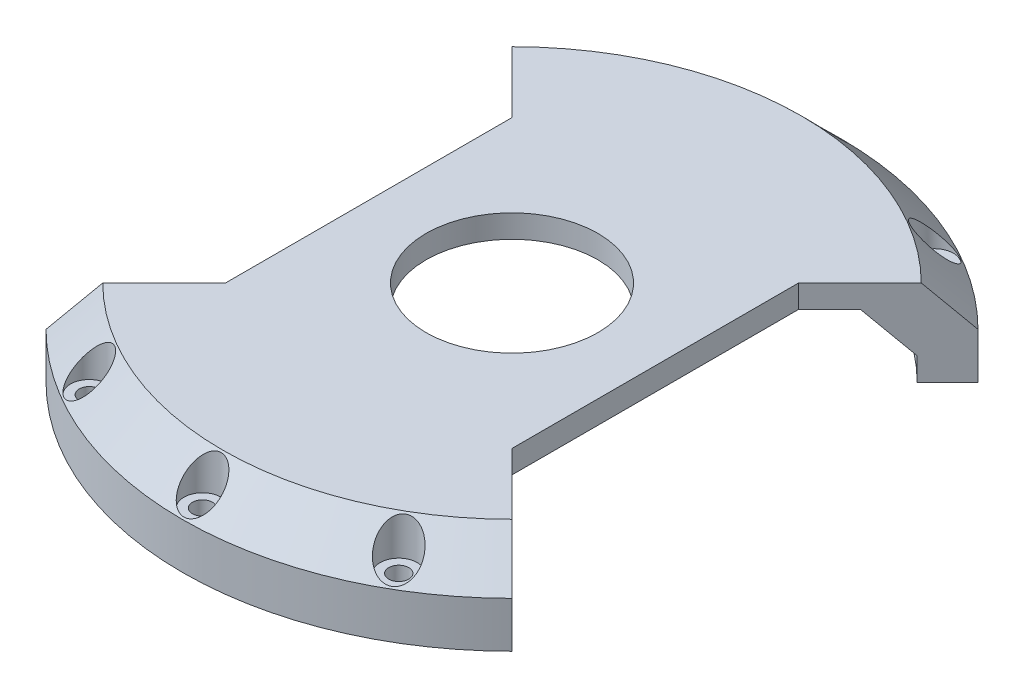
SolidWorks part; units mm, degrees
ref_plane "Front Plane" through (0, 0, 0) normal (0, 0, 1) x (1, 0, 0)
ref_plane "Top Plane" through (0, 0, 0) normal (0, 1, 0) x (1, 0, 0)
ref_plane "Right Plane" through (0, 0, 0) normal (1, 0, 0) x (0, 0, -1)
sketch "Sketch1" plane through (0, 0, 0) normal (0, 1, 0) x (1, 0, 0)
  circle A0 centre (0, 0) radius 57.5
  dimension "D1" = 115
extrude "Boss-Extrude1" add sketch "Sketch1" along normal blind 15
sketch "Sketch2" plane through (0, 0, 0) normal (0, -1, 0) x (1, 0, 0)
  circle A0 centre (0, 0) radius 50
  dimension "D1" = 100
extrude "Cut-Extrude1" cut sketch "Sketch2" against normal blind 11
sketch "Sketch3" plane through (0, 15, 0) normal (0, 1, 0) x (1, 0, 0)
  circle A0 centre (0, 0) radius 54 construction
  circle A1 centre (0, 54) radius 1.75
  circle A2 centre (27, 46.7654) radius 1.75
  circle A3 centre (46.7654, 27) radius 1.75
  circle A4 centre (54, 0) radius 1.75
  circle A5 centre (46.7654, -27) radius 1.75
  circle A6 centre (27, -46.7654) radius 1.75
  circle A7 centre (0, -54) radius 1.75
  circle A8 centre (-27, -46.7654) radius 1.75
  circle A9 centre (-46.7654, -27) radius 1.75
  circle A10 centre (-54, 0) radius 1.75
  circle A11 centre (-46.7654, 27) radius 1.75
  circle A12 centre (-27, 46.7654) radius 1.75
  circle A13 centre (0, 0) radius 15
  point P29 (0, 0)
  dimension "D1" = 108
  dimension "D2" = 3.5
  dimension "D4" = 30
  dimension "D3" = 12
extrude "Cut-Extrude2" cut sketch "Sketch3" against normal blind 15
sketch "Sketch4" plane through (0, 15, 0) normal (0, 1, 0) x (1, 0, 0)
  line L0 (25, 25) -> (40.6586, 40.6586)
  line L1 (-25, 25) -> (25, 25) construction
  line L2 (-25, 25) -> (-25, -25) construction
  line L3 (-25, -25) -> (25, -25) construction
  line L4 (25, 25) -> (25, -25)
  line L5 (-25, 25) -> (25, -25) construction
  line L6 (-25, -25) -> (25, 25) construction
  line L7 (25, -25) -> (40.6586, -40.6586)
  circle A0 centre (0, 0) radius 57.5 construction
  arc A1 (40.6586, -40.6586) -> (40.6586, 40.6586) centre (0, 0) ccw
  point P0 (0, 0)
  point P11 (40.6586, 40.6586)
  dimension "D1" = 50
extrude "Cut-Extrude3" cut sketch "Sketch4" against normal blind 15
mirror "Mirror1" about plane through (0, 0, 0) normal (1, 0, 0) of "Cut-Extrude3"
chamfer "Chamfer1" distance 7 angle 45 4 edges at (0, 15, -57.5) (0, 15, 57.5) (0, 11, 50) (0, 11, -50)
sketch "Sketch5" plane through (0, 15, 0) normal (0, 1, 0) x (1, 0, 0)
  circle A0 centre (0, 0) radius 54 construction
  circle A1 centre (0, 54) radius 3.25
  circle A2 centre (27, 46.7654) radius 3.25
  circle A3 centre (46.7654, 27) radius 3.25
  circle A4 centre (54, 0) radius 3.25
  circle A5 centre (46.7654, -27) radius 3.25
  circle A6 centre (27, -46.7654) radius 3.25
  circle A7 centre (0, -54) radius 3.25
  circle A8 centre (-27, -46.7654) radius 3.25
  circle A9 centre (-46.7654, -27) radius 3.25
  circle A10 centre (-54, 0) radius 3.25
  circle A11 centre (-46.7654, 27) radius 3.25
  circle A12 centre (-27, 46.7654) radius 3.25
  point P32 (0, 0)
  dimension "D1" = 6.5
  dimension "D2" = 12
extrude "Cut-Extrude4" cut sketch "Sketch5" against normal blind 7
